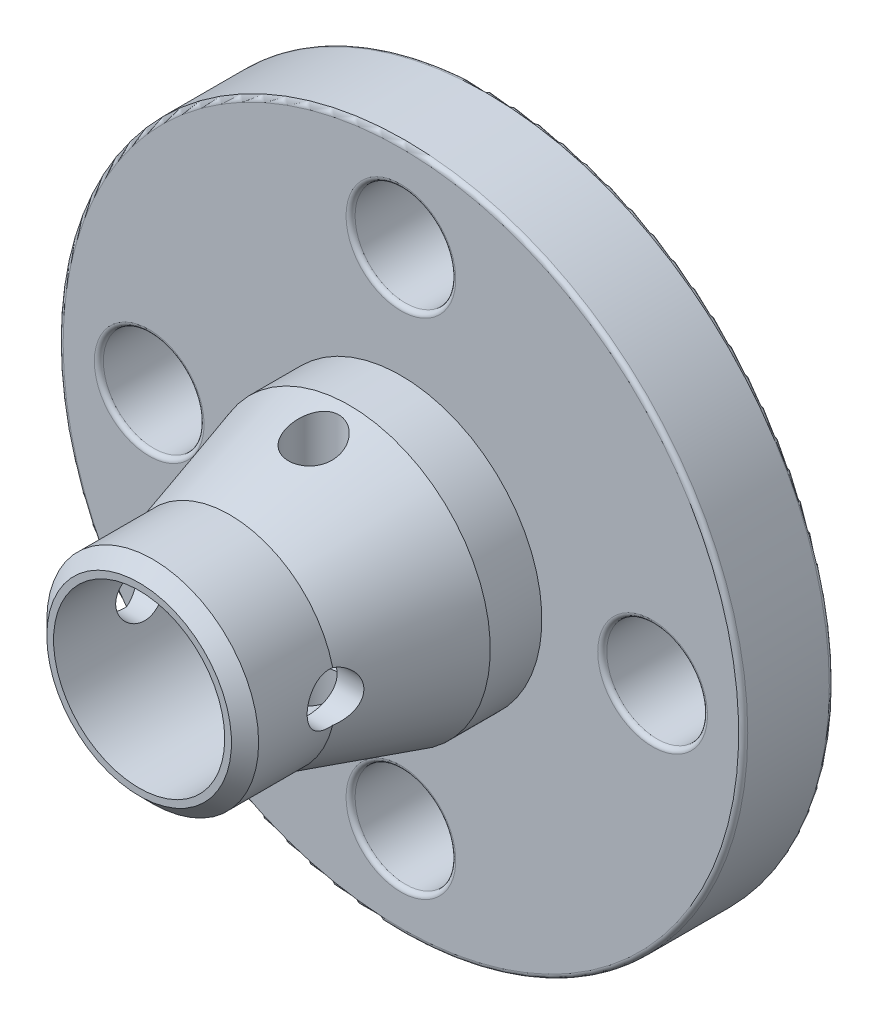
SolidWorks part; units mm, degrees
ref_plane "Front Plane" through (0, 0, 0) normal (0, 0, 1) x (1, 0, 0)
ref_plane "Top Plane" through (0, 0, 0) normal (0, 1, 0) x (1, 0, 0)
ref_plane "Right Plane" through (0, 0, 0) normal (1, 0, 0) x (0, 0, -1)
sketch "Sketch1" plane through (0, 0, 0) normal (1, 0, 0) x (0, 0, -1)
  line L0 (-27.7813, 0) -> (27.7813, 0) construction
  line L1 (27.7813, 13.4937) -> (27.7812, 53.975)
  line L2 (27.7812, 53.975) -> (13.4938, 53.975)
  line L3 (13.4938, 53.975) -> (13.4937, 24.6062)
  line L4 (13.4937, 24.6062) -> (-13.4938, 16.7005)
  line L5 (-13.4938, 16.7005) -> (-27.7812, 16.7005)
  line L6 (-27.7812, 16.7005) -> (-27.7813, 13.4937)
  line L7 (-27.7813, 13.4937) -> (27.7813, 13.4937)
  circle A0 centre (27.7813, 39.6875) radius 7.9375
  point P16 (27.7813, 39.6875)
  dimension "Bolt Size" = 15.875
  dimension "Flange OD" = 107.95
  dimension "Pipe Size" = 26.9875
  dimension "Hub at Chimney" = 33.401
  dimension "Hub OD Base" = 49.2125
  dimension "Flange Thickness" = 14.2875
  dimension "Length" = 55.5625
  dimension "Bolt O Diameter" = 79.375
sketch "Sketch2" plane through (0, 0, 0) normal (1, 0, 0) x (0, 0, -1)
  line L0 (-27.7812, 16.7005) -> (-27.7813, 13.4937) construction
  line L1 (-13.4938, 16.7005) -> (-27.7812, 16.7005) construction
  line L2 (13.4937, 24.6062) -> (-13.4938, 16.7005) construction
  line L3 (13.4938, 53.975) -> (13.4937, 24.6062) construction
  line L4 (27.7812, 53.975) -> (13.4938, 53.975) construction
  line L5 (27.7813, 13.4937) -> (27.7812, 53.975) construction
  line L6 (-27.7813, 13.4937) -> (27.7813, 13.4937) construction
  line L7 (-27.7812, 16.7005) -> (-27.7813, 13.4937)
  line L8 (-13.4938, 16.7005) -> (-27.7812, 16.7005)
  line L9 (13.4937, 24.6062) -> (-13.4938, 16.7005)
  line L10 (13.4938, 53.975) -> (13.4937, 24.6062)
  line L11 (27.7812, 53.975) -> (13.4938, 53.975)
  line L12 (27.7813, 13.4937) -> (27.7812, 53.975)
  line L13 (-27.7813, 13.4937) -> (27.7813, 13.4937)
revolve "Revolve1" add sketch "Sketch2" angle 360 about L0
sketch "Sketch3" plane through (0, 0, -13.4937) normal (0, 0, 1) x (1, 0, 0)
  line L0 (-13.4937, 0) -> (-16.7005, 0) construction
  circle A0 centre (0, 39.6875) radius 7.9375
  circle A1 centre (0, 0) radius 13.4937 construction
  circle A2 centre (0, 0) radius 16.7005 construction
  circle A5 centre (0, 0) radius 16.7005 construction
  dimension "D1" = 15.875
extrude "Cut-Extrude1" cut sketch "Sketch3" against normal through all
pattern_circular "CirPattern1" count 4 over 360 about axis through (0, 0, 27.7813) along (0, 0, -1) of "Cut-Extrude1"
fillet "Fillet1" radius 2.8575 1 edges at (24.6062, 0, -13.4937)
chamfer "Chamfer1" distance 2.1431 angle 45 1 edges at (16.7005, 0, 27.7812)
fillet "Fillet2" radius 0.7144 11 edges at (53.975, 0, -27.7812) (53.975, 0, -13.4937) (13.4937, 0, -27.7813) (7.9375, 39.6875, -27.7813) (39.6875, -7.9375, -27.7813) (-39.6875, 7.9375, -27.7813) (-7.9375, -39.6875, -27.7813) (7.9375, 39.6875, -13.4937) (39.6875, -7.9375, -13.4937) (-39.6875, 7.9375, -13.4937) (-7.9375, -39.6875, -13.4937)
sketch "Sketch4" plane through (0, 0, 27.7813) normal (0, 0, 1) x (1, 0, 0)
  circle A0 centre (0, 0) radius 22.225
  circle A1 centre (0, 0) radius 68.8926
  dimension "D1" = 44.45
  dimension "D2" = 137.7852
extrude "Cut-Extrude2" cut sketch "Sketch4" against normal up to surface (41.275 mm away) up to face at (-53.2606, 0, -13.4937)
sketch "Sketch5" plane through (0, 0, -27.7813) normal (0, 0, -1) x (-1, 0, 0)
  circle A0 centre (0, 0) radius 22.225
  dimension "D1" = 44.45
extrude "Cut-Extrude3" cut sketch "Sketch5" against normal offset from surface (6.35 mm away) 6.35 up to face at (14.2081, 0, -27.7813)
sketch "Sketch6" plane through (0, 0, 0) normal (0, 1, 0) x (1, 0, 0)
  line L0 (-22.225, 13.4937) -> (22.225, 13.4937) construction
  line L1 (-14.5574, -27.7813) -> (14.5574, -27.7813) construction
  line L2 (0, -27.7813) -> (0, -14.0229) construction
  line L3 (0, -14.0229) -> (0, -0.2646) construction
  line L4 (0, -0.2646) -> (0, 13.4937) construction
  circle A0 centre (0, -0.2646) radius 3.9688
  point P0 (0, 13.4937)
  point P1 (0, -27.7813)
  point P4 (0, -14.0229)
  point P7 (0, -0.2646)
  dimension "D1" = 7.9375
extrude "Cut-Extrude4" cut sketch "Sketch6" against normal through all both and the other way through all
sketch "Sketch7" plane through (0, 0, 0) normal (1, 0, 0) x (0, 0, -1)
  line L0 (13.4937, 22.225) -> (13.4937, -22.225) construction
  line L1 (-27.7813, 14.5574) -> (-27.7813, -14.5574) construction
  line L2 (-27.7813, 0) -> (-14.0229, 0) construction
  line L3 (-14.0229, 0) -> (-0.2646, 0) construction
  line L4 (-0.2646, 0) -> (13.4937, 0) construction
  circle A0 centre (-14.0229, 0) radius 3.9687
  point P0 (13.4937, 0)
  point P1 (-27.7813, 0)
  point P4 (-14.0229, 0)
  point P7 (-0.2646, 0)
  dimension "D1" = 7.9375
extrude "Cut-Extrude5" cut sketch "Sketch7" against normal through all both and the other way through all
equation "\"D1@Sketch3\"=\"bolt size@sketch1\""
equation "\"D1@Fillet1\"=\"Flange Thickness@Sketch1\"*0.2"
equation "\"D1@Chamfer1\"=\"Flange Thickness@Sketch1\"*0.15"
equation "\"D1@Fillet2\"=\"flange thickness@sketch1\"*0.05"
